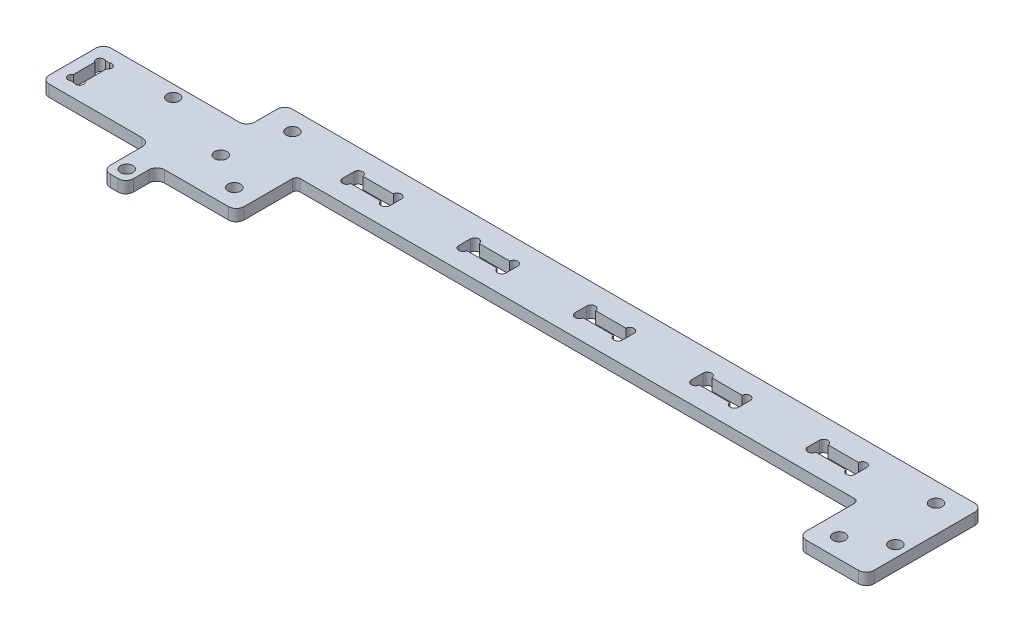
SolidWorks part; units mm, degrees
material "玻纤板"
ref_plane "前视基准面" through (0, 0, 0) normal (0, 0, 1) x (1, 0, 0)
ref_plane "上视基准面" through (0, 0, 0) normal (0, 1, 0) x (1, 0, 0)
ref_plane "右视基准面" through (0, 0, 0) normal (1, 0, 0) x (0, 0, -1)
sketch "草图1" plane through (0, 0, 0) normal (0, 1, 0) x (1, 0, 0)
  line L0 (78, -10) -> (78, -15) construction
  line L1 (-90, -15) -> (-72.5, -15)
  line L2 (-90, -15) -> (-90, 15)
  line L3 (-90, 15) -> (90, 15)
  line L4 (90, -15) -> (90, 15)
  line L5 (0, 15) -> (0, -15) construction
  line L6 (-90, 0) -> (90, 0) construction
  line L7 (-72.5, 0.5) -> (72.5, 0.5)
  line L8 (-72.5, 0.5) -> (-72.5, -15)
  line L10 (72.5, 0.5) -> (72.5, -15)
  line L11 (0, -15) -> (0, 0.5) construction
  line L12 (-72.5, -7.25) -> (72.5, -7.25) construction
  line L13 (72.5, -15) -> (90, -15)
  line L14 (-83, 10) -> (-78, -10) construction
  circle A0 centre (78, -10) radius 1.6
  circle A1 centre (-78, -10) radius 1.6
  circle A2 centre (-83, 10) radius 1.6
  circle A4 centre (83, 10) radius 1.6
  point P0 (0, 0)
  point P4 (0, -7.25)
  dimension "D3" = 3.2
  dimension "D7" = 10.5
  dimension "D8" = 3.2
  dimension "D1" = 156
  dimension "D2" = 145
  dimension "D4" = 180
  dimension "D5" = 30
  dimension "D6" = 5
  dimension "D9" = 25
  dimension "D10" = 5
extrude "凸台-拉伸1" add sketch "草图1" along normal blind 3
ref_axis "基准轴1" through (-78, 3, 10) along (0, -1, 0)
ref_axis "基准轴2" through (-83, 3, -10) along (0, -1, 0)
ref_plane "基准面1" through (-75.7647, 0, 18.9412) normal (-0.9701, 0, 0.2425) x (0.2425, 0, 0.9701)
sketch "草图3" plane through (0, 3, 0) normal (0, 1, 0) x (1, 0, 0)
  line L0 (0, 0.5) -> (0, 15) construction
  line L1 (-72.5, 0.5) -> (72.5, 0.5) construction
  line L2 (90, 15) -> (-90, 15) construction
  line L7 (-90, 15) -> (-90, -15) construction
  line L8 (-90, -15) -> (-72.5, -15) construction
  circle A13 centre (87, -4.5) radius 1.6
  circle A40 centre (-87, -4.5) radius 1.6
  dimension "D2" = 3.2
  dimension "D1" = 3
  dimension "D3" = 10.5
extrude "切除-拉伸1" cut sketch "草图3" against normal through all
sketch "草图4" plane through (0, 0, 0) normal (0, -1, 0) x (1, 0, 0)
  line L0 (0, 0) -> (0, -15) construction
  line L1 (66, -9) -> (54, -9)
  line L2 (66, -9) -> (66, -6)
  line L3 (66, -6) -> (54, -6)
  line L4 (54, -9) -> (54, -6)
  line L5 (60, -6) -> (60, -9) construction
  line L6 (66, -7.5) -> (54, -7.5) construction
  line L7 (90, -15) -> (-90, -15) construction
  line L8 (0, -7.5) -> (54, -7.5) construction
  line L9 (36, -9) -> (36, -6)
  line L10 (36, -9) -> (24, -9)
  line L11 (24, -9) -> (24, -6)
  line L12 (36, -6) -> (24, -6)
  line L13 (6, -9) -> (6, -6)
  line L14 (6, -9) -> (-6, -9)
  line L15 (-6, -9) -> (-6, -6)
  line L16 (6, -6) -> (-6, -6)
  line L17 (-24, -9) -> (-24, -6)
  line L18 (-24, -9) -> (-36, -9)
  line L19 (-36, -9) -> (-36, -6)
  line L20 (-24, -6) -> (-36, -6)
  line L21 (-54, -9) -> (-54, -6)
  line L22 (-54, -9) -> (-66, -9)
  line L23 (-66, -9) -> (-66, -6)
  line L24 (-54, -6) -> (-66, -6)
  point P56 (60, -7.5)
  dimension "D1" = 12
  dimension "D2" = 3
  dimension "D3" = 60
  dimension "D5" = 30
  dimension "D4" = 5
fillet "圆角1" radius 1 2 edges at (72.5, 1.5, -0.5) (-72.5, 1.5, -0.5)
extrude "切除-拉伸2" cut sketch "草图4" against normal through all
sketch "草图5" plane through (0, 0, 0) normal (0, -1, 0) x (1, 0, 0)
  line L0 (54, -9) -> (66, -9) construction
  line L1 (54, -7.5) -> (60, -7.5) construction
  line L2 (54, -6) -> (54, -9) construction
  line L3 (60, -7.5) -> (60, -6) construction
  line L4 (66, -6) -> (54, -6) construction
  line L5 (24, -7.5) -> (30, -7.5) construction
  line L6 (30, -7.5) -> (30, -6) construction
  line L7 (-6, -7.5) -> (0, -7.5) construction
  line L8 (0, -7.5) -> (0, -6) construction
  line L9 (-36, -7.5) -> (-30, -7.5) construction
  line L10 (-30, -7.5) -> (-30, -6) construction
  line L11 (-66, -7.5) -> (-60, -7.5) construction
  line L12 (-60, -7.5) -> (-60, -6) construction
  circle A0 centre (65, -9) radius 1
  circle A1 centre (55, -9) radius 1
  circle A2 centre (55, -6) radius 1
  circle A3 centre (65, -6) radius 1
  circle A4 centre (35, -9) radius 1
  circle A5 centre (25, -9) radius 1
  circle A6 centre (25, -6) radius 1
  circle A7 centre (35, -6) radius 1
  circle A8 centre (5, -9) radius 1
  circle A9 centre (-5, -9) radius 1
  circle A10 centre (-5, -6) radius 1
  circle A11 centre (5, -6) radius 1
  circle A12 centre (-25, -9) radius 1
  circle A13 centre (-35, -9) radius 1
  circle A14 centre (-35, -6) radius 1
  circle A15 centre (-25, -6) radius 1
  circle A16 centre (-55, -9) radius 1
  circle A17 centre (-65, -9) radius 1
  circle A18 centre (-65, -6) radius 1
  circle A19 centre (-55, -6) radius 1
  dimension "D1" = 2
  dimension "D3" = 20
  dimension "D2" = 5
extrude "切除-拉伸3" cut sketch "草图5" against normal through all
sketch "草图6" plane through (0, 0, 0) normal (0, -1, 0) x (1, 0, 0)
  line L4 (36.1, -9) -> (36.1, -6)
  line L5 (33.9046, -5.9) -> (26.0954, -5.9)
  line L6 (23.9, -6) -> (23.9, -9)
  line L7 (26.0954, -9.1) -> (33.9046, -9.1)
  line L8 (66.1, -9) -> (66.1, -6)
  line L9 (63.9046, -5.9) -> (56.0954, -5.9)
  line L10 (53.9, -6) -> (53.9, -9)
  line L11 (56.0954, -9.1) -> (63.9046, -9.1)
  line L12 (66.1, -9) -> (66.1, -6)
  line L13 (63.9046, -5.9) -> (56.0954, -5.9)
  line L14 (53.9, -6) -> (53.9, -9)
  line L15 (56.0954, -9.1) -> (63.9046, -9.1)
  line L16 (6.1, -9) -> (6.1, -6)
  line L17 (3.9046, -5.9) -> (-3.9046, -5.9)
  line L18 (-6.1, -6) -> (-6.1, -9)
  line L19 (-3.9046, -9.1) -> (3.9046, -9.1)
  line L20 (-23.9, -9) -> (-23.9, -6)
  line L21 (-26.0954, -5.9) -> (-33.9046, -5.9)
  line L22 (-36.1, -6) -> (-36.1, -9)
  line L23 (-33.9046, -9.1) -> (-26.0954, -9.1)
  line L24 (-53.9, -9) -> (-53.9, -6)
  line L25 (-56.0954, -5.9) -> (-63.9046, -5.9)
  line L26 (-66.1, -6) -> (-66.1, -9)
  line L27 (-63.9046, -9.1) -> (-56.0954, -9.1)
  arc A4 (33.9046, -9.1) -> (36.1, -9) centre (35, -9) ccw
  arc A5 (36.1, -6) -> (33.9046, -5.9) centre (35, -6) ccw
  arc A6 (26.0954, -5.9) -> (23.9, -6) centre (25, -6) ccw
  arc A7 (23.9, -9) -> (26.0954, -9.1) centre (25, -9) ccw
  arc A8 (63.9046, -9.1) -> (66.1, -9) centre (65, -9) ccw
  arc A9 (66.1, -6) -> (63.9046, -5.9) centre (65, -6) ccw
  arc A10 (56.0954, -5.9) -> (53.9, -6) centre (55, -6) ccw
  arc A11 (53.9, -9) -> (56.0954, -9.1) centre (55, -9) ccw
  arc A12 (63.9046, -9.1) -> (66.1, -9) centre (65, -9) ccw
  arc A13 (66.1, -6) -> (63.9046, -5.9) centre (65, -6) ccw
  arc A14 (56.0954, -5.9) -> (53.9, -6) centre (55, -6) ccw
  arc A15 (53.9, -9) -> (56.0954, -9.1) centre (55, -9) ccw
  arc A16 (3.9046, -9.1) -> (6.1, -9) centre (5, -9) ccw
  arc A17 (6.1, -6) -> (3.9046, -5.9) centre (5, -6) ccw
  arc A18 (-3.9046, -5.9) -> (-6.1, -6) centre (-5, -6) ccw
  arc A19 (-6.1, -9) -> (-3.9046, -9.1) centre (-5, -9) ccw
  arc A20 (-26.0954, -9.1) -> (-23.9, -9) centre (-25, -9) ccw
  arc A21 (-23.9, -6) -> (-26.0954, -5.9) centre (-25, -6) ccw
  arc A22 (-33.9046, -5.9) -> (-36.1, -6) centre (-35, -6) ccw
  arc A23 (-36.1, -9) -> (-33.9046, -9.1) centre (-35, -9) ccw
  arc A24 (-56.0954, -9.1) -> (-53.9, -9) centre (-55, -9) ccw
  arc A25 (-53.9, -6) -> (-56.0954, -5.9) centre (-55, -6) ccw
  arc A26 (-63.9046, -5.9) -> (-66.1, -6) centre (-65, -6) ccw
  arc A27 (-66.1, -9) -> (-63.9046, -9.1) centre (-65, -9) ccw
  dimension "D3" = 30
  dimension "D1" = 0.1
  dimension "D2" = 5
extrude "切除-拉伸4" cut sketch "草图6" against normal through all
sketch "草图7" plane through (0, 0, 0) normal (0, -1, 0) x (1, 0, 0)
  line L0 (-90, -5.25) -> (-90, 15)
  line L6 (-71.5, -0.5) -> (71.5, -0.5) construction
  line L7 (-90, -15) -> (-90, 15) construction
  line L31 (-124, 7.25) -> (-121, 7.25)
  line L32 (-90, 2.75) -> (-127, 2.75) construction
  line L48 (-90, -5.25) -> (-127, -5.25)
  line L49 (-127, -5.25) -> (-127, 10.75)
  line L50 (-127, 10.75) -> (-99, 10.75)
  line L51 (-106, -2.25) -> (-106, 10.75) construction
  line L52 (-90, 15) -> (-72.5, 15) construction
  line L53 (-93, 15) -> (-90, 15)
  line L59 (-99, 10.75) -> (-99, 23)
  line L60 (-99, 23) -> (-93, 23)
  line L61 (-93, 15) -> (-93, 23)
  line L62 (-96, 19.75) -> (-96, 23) construction
  line L63 (-124, 7.25) -> (-124, -1.75)
  line L64 (-124, -1.75) -> (-121, -1.75)
  line L65 (-121, 7.25) -> (-121, -1.75)
  line L66 (-122.5, -1.75) -> (-122.5, 7.25) construction
  line L67 (-124, 2.75) -> (-121, 2.75) construction
  circle A6 centre (-96, 19.75) radius 1.6
  circle A7 centre (-106, -2.25) radius 1.6
  point P6 (-122.5, 2.75)
  dimension "D5" = 3
  dimension "D11" = 10
  dimension "D12" = 3.2
  dimension "D14" = 3
  dimension "D15" = 22
  dimension "D6" = 20.25
  dimension "D2" = 16
  dimension "D3" = 3.25
  dimension "D4" = 37
  dimension "D8" = 8
  dimension "D9" = 3
  dimension "D10" = 9
  dimension "D16" = 6
extrude "凸台-拉伸2" add sketch "草图7" against normal up to surface (3 mm away) up to face at (-60, 3, -7.5)
sketch "草图8" plane through (0, 3, 0) normal (0, 1, 0) x (1, 0, 0)
  line L0 (-123.005, 1.75) -> (-121.995, 1.75) construction
  line L1 (-121, -2.75) -> (-122.5, -2.75) construction
  line L2 (-121, -7.25) -> (-121, 1.75) construction
  line L3 (-122.5, -2.75) -> (-122.5, -7.25) construction
  line L4 (-124, -7.25) -> (-121, -7.25) construction
  line L5 (-121, 1.75) -> (-124, 1.75) construction
  circle A0 centre (-123.5025, 0.8825) radius 1
  circle A4 centre (-121.4975, 0.8825) radius 1
  circle A5 centre (-121.4975, -6.3825) radius 1
  circle A6 centre (-123.5025, -6.3825) radius 1
  dimension "D1" = 2
  dimension "D2" = 1.01
fillet "圆角3" radius 2 12 edges at (90, 1.5, 15) (72.5, 1.5, 15) (-72.5, 1.5, 15) (90, 1.5, -15) (-127, 1.5, 10.75) (-127, 1.5, -5.25) (-90, 1.5, -5.25) (-90, 1.5, -15) (-93, 1.5, 15) (-93, 1.5, 23) (-99, 1.5, 23) (-99, 1.5, 10.75)
extrude "切除-拉伸5" cut sketch "草图8" against normal through all
